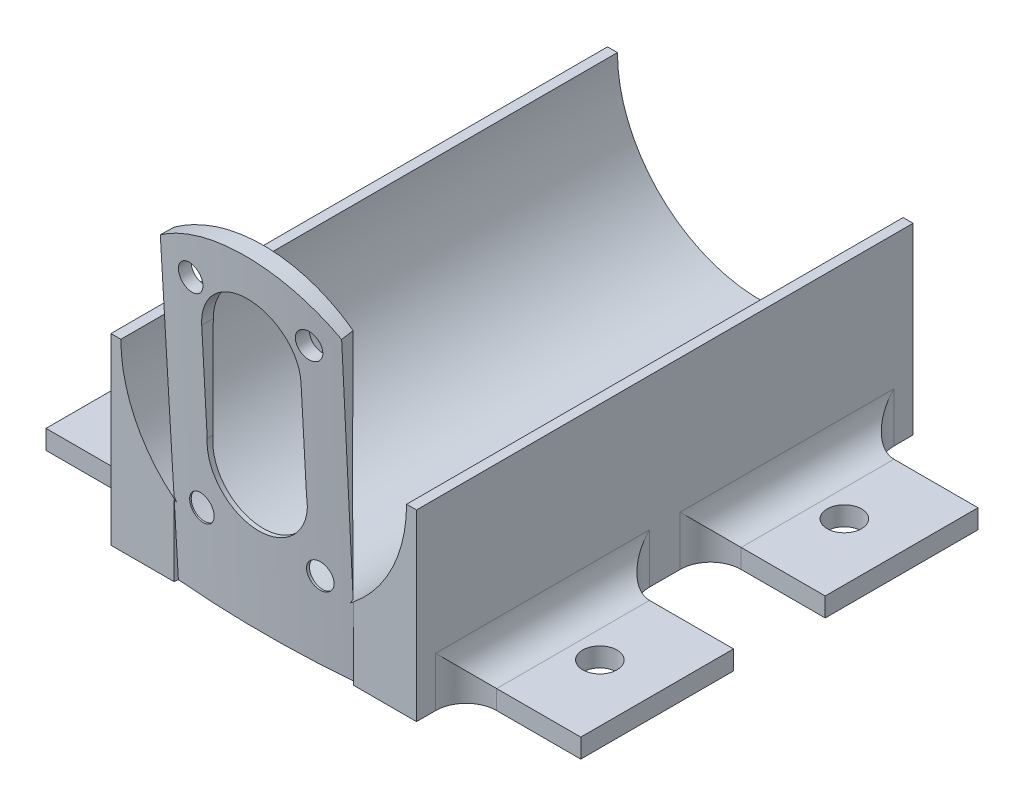
SolidWorks part; units mm, degrees
ref_plane "Plano frontal" through (0, 0, 0) normal (0, 0, 1) x (1, 0, 0)
ref_plane "Plano superior" through (0, 0, 0) normal (0, 1, 0) x (1, 0, 0)
ref_plane "Plano direito" through (0, 0, 0) normal (1, 0, 0) x (0, 0, -1)
sketch "Esboço2" plane through (0, 0, 0) normal (0, 0, 1) x (1, 0, 0)
  line L0 (0, 0) -> (40, 0)
  line L1 (40, 0) -> (40, 24)
  line L2 (0, 24) -> (0, 0)
  arc A0 (40, 24) -> (0, 24) centre (20, 24) ccw
  point P6 (20, 44)
  point P7 (20, 0)
  dimension "D1" = 40
  dimension "D2" = 44
extrude "Ressalto-extrusão1" add sketch "Esboço2" along normal blind 65
sketch "Esboço4" plane through (0, 0, 0) normal (0, 0, -1) x (-1, 0, 0)
  line L0 (-38, 24) -> (-38, 3)
  line L1 (-38, 3) -> (-2, 3)
  line L2 (-2, 3) -> (-2, 24)
  line L3 (0, 0) -> (-40, 0) construction
  arc A0 (-2, 24) -> (-38, 24) centre (-20, 24) ccw
  arc A1 (0, 24) -> (-40, 24) centre (-20, 24) ccw construction
  dimension "D1" = 2
  dimension "D2" = 3
extrude "Corte-extrusão2" cut sketch "Esboço4" against normal blind 40
sketch "Esboço5" plane through (0, 0, 0) normal (0, 0, -1) x (-1, 0, 0)
  line L1 (-20, 8.5) -> (-20, 3)
  line L2 (-38, 3) -> (-2, 3) construction
  circle A0 centre (-20, 24) radius 18.7
  dimension "D1" = 37.4
extrude "Corte-extrusão3" cut sketch "Esboço5" against normal blind 62 contours A0
sketch "Esboço6" plane through (0, 0, 0) normal (0, 0, -1) x (-1, 0, 0)
  line L0 (-38, 18.9315) -> (-38, 3)
  line L1 (-38, 3) -> (-2, 3)
  line L2 (-2, 3) -> (-2, 18.9315)
  arc A2 (-38, 18.9315) -> (-2, 18.9315) centre (-20, 24) ccw
extrude "Ressalto-extrusão2" add sketch "Esboço6" against normal up to surface (40 mm away) up to face at (20, 7.5579, 40)
ref_plane "Plano1" through (20, 0, 0) normal (1, 0, 0) x (0, 0, -1)
sketch "Esboço7" plane through (20, 0, 0) normal (1, 0, 0) x (0, 0, -1)
  line L0 (-65, 0) -> (69, 0) construction
  line L1 (69, 0) -> (69, 339) construction
  line L2 (-65, 0) -> (-83.5, 339)
  line L3 (-65, 0) -> (-61.4012, 0)
  line L4 (-61.4012, 0) -> (-61.4012, 44)
  line L5 (0, 44) -> (-65, 44) construction
  line L6 (-61.4012, 44) -> (-67.4012, 44)
  dimension "D1" = 134
  dimension "D2" = 339
  dimension "D3" = 152.5
  dimension "D4" = 6
revolve "Revolução1" add sketch "Esboço7" angle 10 mid plane about L1 region at (20, 23.8345, 63.8509)
sketch "Esboço3" plane through (0, 0, 65) normal (0, 0, 1) x (1, 0, 0)
  line L0 (13.5, 32.5) -> (13.5, 19.3078)
  line L1 (26.5, 32.5) -> (26.5, 19.3078)
  line L2 (0, 0) -> (20, 0) construction
  circle A0 centre (20, 24) radius 15.5 construction
  circle A1 centre (4.5, 24) radius 1.7
  circle A2 centre (12.25, 37.4234) radius 1.7
  circle A3 centre (27.75, 37.4234) radius 1.7
  circle A4 centre (35.5, 24) radius 1.7
  circle A5 centre (27.75, 10.5766) radius 1.7
  circle A6 centre (12.25, 10.5766) radius 1.7
  arc A7 (13.5, 19.3078) -> (26.5, 19.3078) centre (20, 18.5) ccw
  arc A9 (13.5, 32.5) -> (26.5, 32.5) centre (20, 32.5) cw
  point P17 (20, 24)
  dimension "D1" = 31
  dimension "D2" = 6
  dimension "D3" = 3.4
  dimension "D6" = 14
  dimension "D7" = 6.55
  dimension "D5" = 6.5
  dimension "D4" = 18.5
extrude "Corte-extrusão1" cut sketch "Esboço3" against normal through all and the other way through all
sketch "Esboço9" plane through (20, 0, 0) normal (1, 0, 0) x (0, 0, -1)
  line L0 (-65, 0) -> (-83.5, 339) construction
  line L1 (-65, 0) -> (-83.5, 339)
  line L2 (-65, 0) -> (-67.4558, 0)
  line L3 (-67.4558, 0) -> (-67.4558, 45)
  dimension "D1" = 45
revolve "Corte-Revolução1" cut sketch "Esboço9" angle 10 mid plane about L1 region at (20, 15, 66.6372)
sketch "Esboço10" plane through (0, 0, 0) normal (0, 0, -1) x (-1, 0, 0)
  line L0 (-40, 0) -> (-54.7857, 0)
  line L1 (-54.7857, 0) -> (-54.7857, 47.489)
  line L2 (-54.7857, 47.489) -> (10.9425, 47.489)
  line L3 (0, 0) -> (0, 24)
  line L4 (-40, 24) -> (-40, 0)
  line L5 (-40, 0) -> (0, 0)
  line L6 (0, 0) -> (0, 24)
  line L7 (-40, 24) -> (-40, 0)
  line L8 (-40, 0) -> (0, 0)
  line L9 (10.9425, 47.489) -> (10.9425, 0)
  line L10 (10.9425, 0) -> (0, 0)
  arc A1 (0, 24) -> (-40, 24) centre (-20, 24) ccw
  arc A2 (0, 24) -> (-40, 24) centre (-20, 24) ccw
  line M6 (0, 0) -> (0, 24)
  arc M7 (0, 24) -> (-40, 24) centre (-20, 24) ccw
  line M8 (-40, 24) -> (-40, 0)
  dimension "D1" = 0
extrude "Corte-extrusão4" cut sketch "Esboço10" against normal through all contours L10 L9 L2 L1 L0 M8 M7 M6 region at (47.3929, 0.8109, 0)
sketch "Esboço12" plane through (0, 0, 0) normal (0, -1, 0) x (1, 0, 0)
  line L0 (0, 58.5) -> (-15, 58.5)
  line L1 (0, 65) -> (0, 0) construction
  line L2 (-15, 58.5) -> (-15, 6.5)
  line L3 (-15, 6.5) -> (0, 6.5)
  line L7 (0, 58.5) -> (0, 6.5)
  line L10 (20, 0) -> (20, 73.543) construction
  line L11 (0, 0) -> (40, 0) construction
  line L12 (20, -23.65) -> (20, 23.65) construction
  line L13 (-15, 38.5) -> (0, 38.5)
  line L14 (-15, 26.5) -> (0, 26.5)
  line L15 (55, 26.5) -> (40, 26.5)
  line L16 (55, 38.5) -> (40, 38.5)
  line L17 (40, 58.5) -> (40, 6.5)
  line L18 (55, 6.5) -> (40, 6.5)
  line L19 (55, 58.5) -> (55, 6.5)
  line L20 (40, 58.5) -> (55, 58.5)
  circle A0 centre (-7.5, 48.5) radius 2.25
  circle A1 centre (-7.5, 16.5) radius 2.25
  circle A2 centre (47.5, 16.5) radius 2.25
  circle A3 centre (47.5, 48.5) radius 2.25
  point P11 (0, 32.5)
  point P13 (-15, 32.5)
  point P14 (0, 32.5)
  line M11 (0, 65) -> (0, 0)
  line M13 (40, 0) -> (40, 65)
  dimension "D6" = 4.5
  dimension "D1" = 20
  dimension "D2" = 20
  dimension "D3" = 12
  dimension "D4" = 15
  dimension "D5" = 10
  dimension "D7" = 10
  dimension "D8" = 7.5
  dimension "D9" = 7.5
extrude "Ressalto-extrusão3" add sketch "Esboço12" against normal blind 2.5 contours L2 L13 L0 A0 M11 | L14 L2 L3 A1 M11 | L19 L15 L18 A2 M13 | L20 L16 L19 A3 M13 region at (-0.25, 0, 48.5) region at (-0.25, 0, 16.5) region at (54.75, 0, 16.5) region at (47.5, 0, 38.75)
sketch "Esboço13" plane through (20, 0, 0) normal (1, 0, 0) x (0, 0, -1)
  line L0 (0, 0) -> (0, 24) construction
  line L1 (-60, 47.1603) -> (-60.1462, 24)
  line L2 (0, 24) -> (-60.1462, 24)
  line L4 (-60, 47.1603) -> (0, 47.1603)
  line L5 (0, 47.1603) -> (0, 24)
  dimension "D1" = 60
extrude "Corte-extrusão5" cut sketch "Esboço13" against normal mid plane 45
sketch "Esboço14" plane through (20, 0, 0) normal (1, 0, 0) x (0, 0, -1)
  line L0 (-29.9017, 5.3) -> (-29.9017, 43.9101) construction
  line L1 (-61.4012, 5.3) -> (0, 5.3) construction
  line L2 (-65.0282, 42.7) -> (-60.0282, 42.7)
  line L4 (-29.9017, 24.605) -> (-55.5712, 24.605) construction
  line L5 (-60.2016, 24.605) -> (-60.0282, 42.7)
  line L7 (-65.0282, 42.7) -> (-65.2016, 24.605)
  line L9 (-65.2016, 24.605) -> (-60.2016, 24.605)
  dimension "D1" = 5
  dimension "D2" = 5
revolve "Corte-Revolução2" cut sketch "Esboço14" angle 360 about L4
fillet "Filete1" radius 4 12 edges at (0, 1.25, 58.5) (0, 1.25, 26.5) (0, 2.5, 48.5) (0, 1.25, 38.5) (0, 2.5, 16.5) (0, 1.25, 6.5) (40, 1.25, 58.5) (40, 1.25, 38.5) (40, 1.25, 26.5) (40, 1.25, 6.5) (40, 2.5, 16.5) (40, 2.5, 48.5)
sketch "Esboço15" plane through (0, 0, 0) normal (0, 0, -1) x (-1, 0, 0)
  line L0 (-38.7, 24) -> (-43.4487, 24)
  line L1 (-43.4487, 24) -> (-43.4487, 44.8414)
  line L2 (-43.4487, 44.8414) -> (3.6355, 44.8414)
  line L3 (3.6355, 44.8414) -> (3.6355, 24)
  line L4 (3.6355, 24) -> (-1.3, 24)
  arc A0 (-38.7, 24) -> (-1.3, 24) centre (-20, 24) ccw
extrude "Corte-extrusão8" cut sketch "Esboço15" against normal up to surface (64.9768 mm away) up to face at (20, 22.4513, 65.055)
